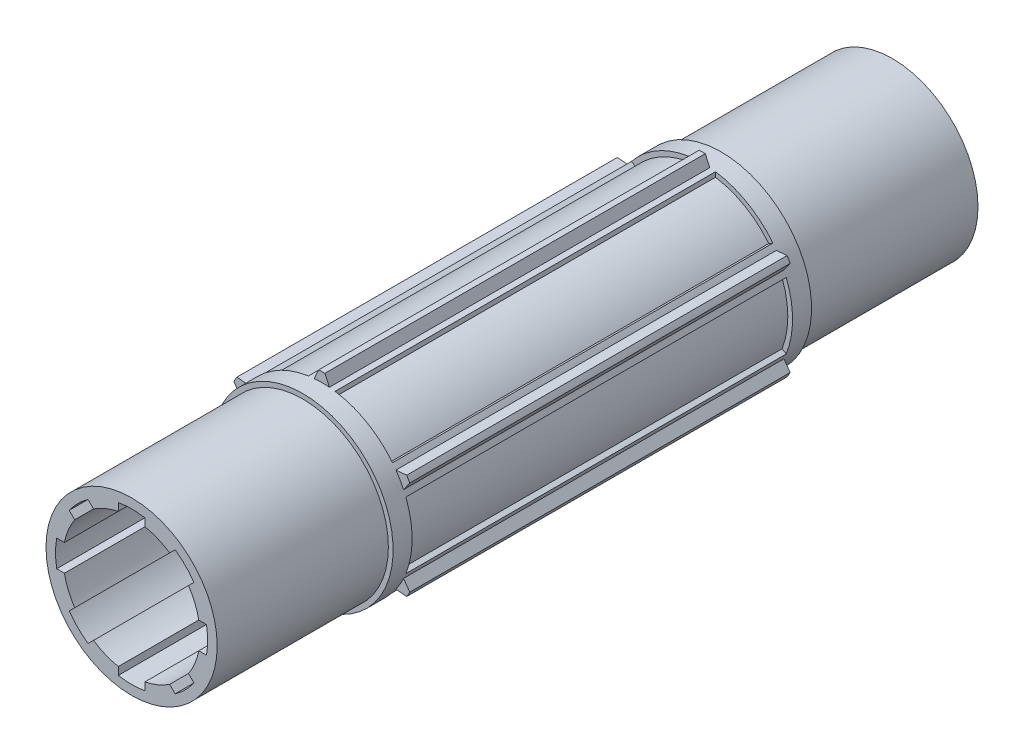
SolidWorks part; units mm, degrees
ref_plane "Front Plane" through (0, 0, 0) normal (0, 0, 1) x (1, 0, 0)
ref_plane "Top Plane" through (0, 0, 0) normal (0, 1, 0) x (1, 0, 0)
ref_plane "Right Plane" through (0, 0, 0) normal (1, 0, 0) x (0, 0, -1)
sketch "Sketch1" plane through (0, 0, 0) normal (0, 0, 1) x (1, 0, 0)
  line L0 (0, 0) -> (0, 33.7674) construction
  line L17 (-3.5, 19.6914) -> (-3.5, 17.6564)
  line L18 (3.5, 19.6914) -> (3.5, 17.6564)
  line L19 (11.449, 16.3988) -> (10.0101, 14.9599)
  line L20 (16.3988, 11.449) -> (14.9599, 10.0101)
  line L21 (19.6914, 3.5) -> (17.6564, 3.5)
  line L22 (19.6914, -3.5) -> (17.6564, -3.5)
  line L23 (16.3988, -11.449) -> (14.9599, -10.0101)
  line L24 (11.449, -16.3988) -> (10.0101, -14.9599)
  line L25 (3.5, -19.6914) -> (3.5, -17.6564)
  line L26 (-3.5, -19.6914) -> (-3.5, -17.6564)
  line L27 (-11.449, -16.3988) -> (-10.0101, -14.9599)
  line L28 (-16.3988, -11.449) -> (-14.9599, -10.0101)
  line L29 (-19.6914, -3.5) -> (-17.6564, -3.5)
  line L30 (-19.6914, 3.5) -> (-17.6564, 3.5)
  line L31 (-16.3988, 11.449) -> (-14.9599, 10.0101)
  line L32 (-11.449, 16.3988) -> (-10.0101, 14.9599)
  circle A17 centre (0, 0) radius 22.5
  arc A18 (-11.449, 16.3988) -> (-16.3988, 11.449) centre (0, 0) ccw
  arc A19 (-3.5, 17.6564) -> (-10.0101, 14.9599) centre (0, 0) ccw
  arc A20 (3.5, 19.6914) -> (-3.5, 19.6914) centre (0, 0) ccw
  arc A21 (10.0101, 14.9599) -> (3.5, 17.6564) centre (0, 0) ccw
  arc A22 (-14.9599, 10.0101) -> (-17.6564, 3.5) centre (0, 0) ccw
  arc A23 (-19.6914, 3.5) -> (-19.6914, -3.5) centre (0, 0) ccw
  arc A24 (-17.6564, -3.5) -> (-14.9599, -10.0101) centre (0, 0) ccw
  arc A25 (-16.3988, -11.449) -> (-11.449, -16.3988) centre (0, 0) ccw
  arc A26 (-10.0101, -14.9599) -> (-3.5, -17.6564) centre (0, 0) ccw
  arc A27 (-3.5, -19.6914) -> (3.5, -19.6914) centre (0, 0) ccw
  arc A28 (3.5, -17.6564) -> (10.0101, -14.9599) centre (0, 0) ccw
  arc A29 (11.449, -16.3988) -> (16.3988, -11.449) centre (0, 0) ccw
  arc A30 (14.9599, -10.0101) -> (17.6564, -3.5) centre (0, 0) ccw
  arc A31 (19.6914, -3.5) -> (19.6914, 3.5) centre (0, 0) ccw
  arc A32 (17.6564, 3.5) -> (14.9599, 10.0101) centre (0, 0) ccw
  arc A33 (16.3988, 11.449) -> (11.449, 16.3988) centre (0, 0) ccw
  point P39 (0, 0)
  dimension "D1" = 3.5
  dimension "D2" = 3.5
extrude "Boss-Extrude1" add sketch "Sketch1" along normal blind 200
sketch "Sketch3" plane through (0, 0, 0) normal (0, 0, 1) x (1, 0, 0)
  line L0 (0, 0) -> (0, 28.873) construction
  line L1 (-2, 23.6656) -> (-0.8006, 26.2378)
  line L2 (2, 23.6656) -> (0.8006, 26.2378)
  line L3 (-3.5, 22.2261) -> (-3.5, 23.4907)
  line L4 (3.5, 22.2261) -> (3.5, 23.4907)
  line L5 (17.4984, 14.1441) -> (18.5935, 14.7764)
  line L6 (19.495, 13.5649) -> (22.3223, 13.8122)
  line L7 (21.495, 10.1008) -> (23.1229, 12.4256)
  line L8 (20.9984, 8.082) -> (22.0935, 8.7143)
  line L9 (20.9984, -8.082) -> (22.0935, -8.7143)
  line L10 (21.495, -10.1008) -> (23.1229, -12.4256)
  line L11 (19.495, -13.5649) -> (22.3223, -13.8122)
  line L12 (17.4984, -14.1441) -> (18.5935, -14.7764)
  line L13 (3.5, -22.2261) -> (3.5, -23.4907)
  line L14 (2, -23.6656) -> (0.8006, -26.2378)
  line L15 (-2, -23.6656) -> (-0.8006, -26.2378)
  line L16 (-3.5, -22.2261) -> (-3.5, -23.4907)
  line L17 (-17.4984, -14.1441) -> (-18.5935, -14.7764)
  line L18 (-19.495, -13.5649) -> (-22.3223, -13.8122)
  line L19 (-21.495, -10.1008) -> (-23.1229, -12.4256)
  line L20 (-20.9984, -8.082) -> (-22.0935, -8.7143)
  line L21 (-20.9984, 8.082) -> (-22.0935, 8.7143)
  line L22 (-21.495, 10.1008) -> (-23.1229, 12.4256)
  line L23 (-19.495, 13.5649) -> (-22.3223, 13.8122)
  line L24 (-17.4984, 14.1441) -> (-18.5935, 14.7764)
  arc A0 (-20.9984, -8.082) -> (-17.4984, -14.1441) centre (0, 0) ccw
  arc A1 (-2, 23.6656) -> (-3.5, 23.4907) centre (0, 0) ccw
  arc A2 (0.8006, 26.2378) -> (-0.8006, 26.2378) centre (0, 0) ccw
  arc A3 (2, 23.6656) -> (3.5, 23.4907) centre (0, 0) cw
  arc A4 (19.495, 13.5649) -> (18.5935, 14.7764) centre (0, 0) ccw
  arc A5 (23.1229, 12.4256) -> (22.3223, 13.8122) centre (0, 0) ccw
  arc A6 (21.495, 10.1008) -> (22.0935, 8.7143) centre (0, 0) cw
  arc A7 (21.495, -10.1008) -> (22.0935, -8.7143) centre (0, 0) ccw
  arc A8 (22.3223, -13.8122) -> (23.1229, -12.4256) centre (0, 0) ccw
  arc A9 (19.495, -13.5649) -> (18.5935, -14.7764) centre (0, 0) cw
  arc A10 (2, -23.6656) -> (3.5, -23.4907) centre (0, 0) ccw
  arc A11 (-0.8006, -26.2378) -> (0.8006, -26.2378) centre (0, 0) ccw
  arc A12 (-2, -23.6656) -> (-3.5, -23.4907) centre (0, 0) cw
  arc A13 (-19.495, -13.5649) -> (-18.5935, -14.7764) centre (0, 0) ccw
  arc A14 (-23.1229, -12.4256) -> (-22.3223, -13.8122) centre (0, 0) ccw
  arc A15 (-21.495, -10.1008) -> (-22.0935, -8.7143) centre (0, 0) cw
  arc A16 (-21.495, 10.1008) -> (-22.0935, 8.7143) centre (0, 0) ccw
  arc A17 (-22.3223, 13.8122) -> (-23.1229, 12.4256) centre (0, 0) ccw
  arc A18 (-19.495, 13.5649) -> (-18.5935, 14.7764) centre (0, 0) cw
  arc A19 (-17.4984, 14.1441) -> (-20.9984, 8.082) centre (0, 0) ccw
  arc A20 (3.5, 22.2261) -> (-3.5, 22.2261) centre (0, 0) ccw
  arc A21 (20.9984, 8.082) -> (17.4984, 14.1441) centre (0, 0) ccw
  arc A22 (17.4984, -14.1441) -> (20.9984, -8.082) centre (0, 0) ccw
  arc A23 (-3.5, -22.2261) -> (3.5, -22.2261) centre (0, 0) ccw
  point P55 (0, 0)
  dimension "D1" = 45
extrude "Boss-Extrude2" add sketch "Sketch3" along normal blind 100 from offset 50
sketch "Sketch4" plane through (0, 0, 200) normal (0, 0, 1) x (1, 0, 0)
  circle A0 centre (0, 0) radius 23.75
  circle A1 centre (0, 0) radius 22.5
  dimension "D1" = 45
  dimension "D2" = 47.5
extrude "Boss-Extrude3" add sketch "Sketch4" along normal blind 5 from surface starting at face at (20.7359, 11.9719, 150)
extrude "Boss-Extrude4" add sketch "Sketch4<2>" against normal blind 5 from surface starting at face at (0, 23.9438, 50)
sketch "Sketch4<2>" plane through (0, 0, 200) normal (0, 0, 1) x (1, 0, 0) same geometry as "Sketch4"
